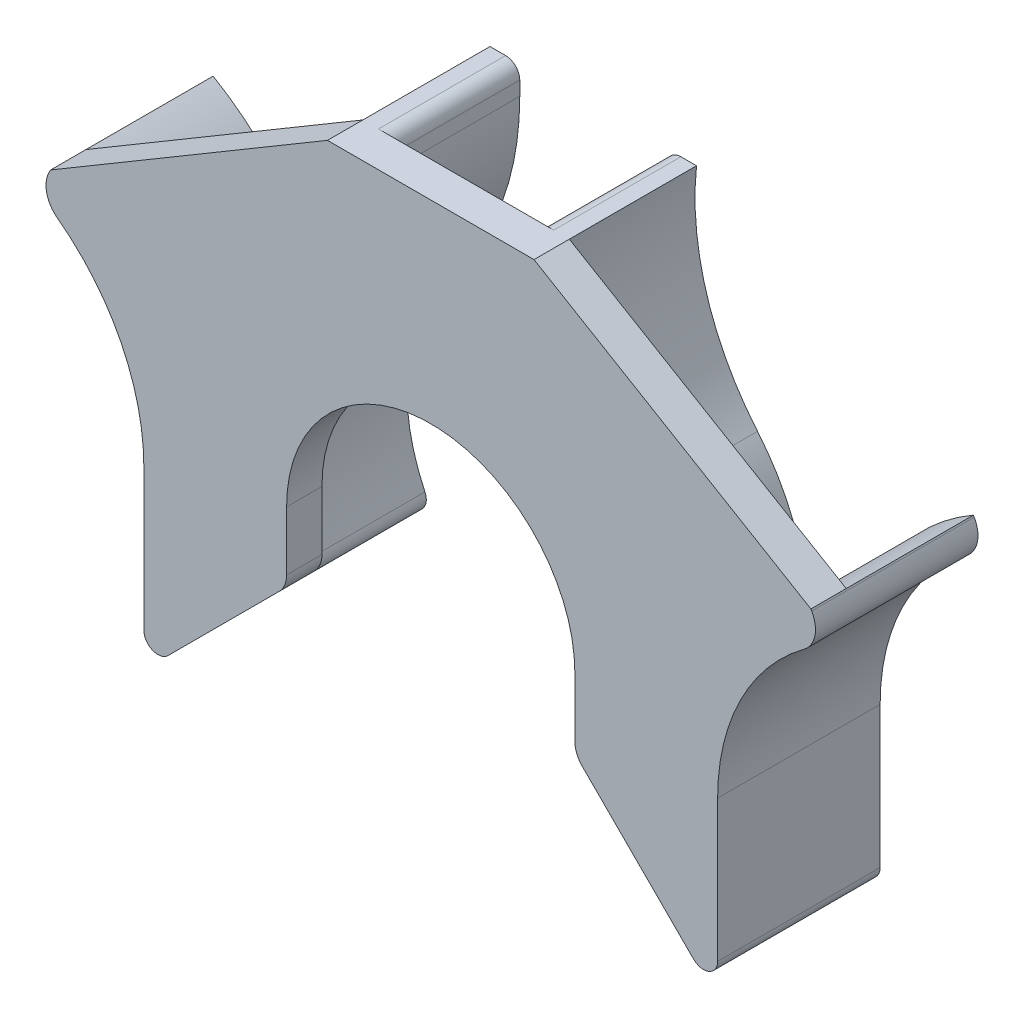
SolidWorks part; units mm, degrees
ref_plane "Front Plane" through (0, 0, 0) normal (0, 0, 1) x (1, 0, 0)
ref_plane "Top Plane" through (0, 0, 0) normal (0, 1, 0) x (1, 0, 0)
ref_plane "Right Plane" through (0, 0, 0) normal (1, 0, 0) x (0, 0, -1)
sketch "Sketch3" plane through (0, 0, 0) normal (0, 0, 1) x (1, 0, 0)
  point P0 (0, 0)
  line B0 (9.9412, 8.3769) -> (9.1765, 7.7326)
  line B1 (-9.1765, 7.7326) -> (-9.9412, 8.3769)
  line B2 (22, -13) -> (22, -2.5981)
  line B3 (20.5, -2.5981) -> (20.5, -13)
  line B4 (28.75, 9.0933) -> (28, 10.3923)
  line B5 (-28, 10.3923) -> (-28.75, 9.0933)
  line B6 (-20.5, -13) -> (-20.5, -2.5981)
  line B7 (-22, -2.5981) -> (-22, -13)
  line B8 (-10.5858, -5.5858) -> (-19.4142, -14.4142)
  line B9 (-19.4142, -14.4142) -> (-18.3536, -15.4749)
  line B10 (-18.3536, -15.4749) -> (-9.5251, -6.6464)
  line B11 (-10, 0) -> (-10, -4.1716)
  line B12 (-8.5, -4.1716) -> (-8.5, 0)
  line B13 (18.3536, -15.4749) -> (19.4142, -14.4142)
  line B14 (19.4142, -14.4142) -> (10.5858, -5.5858)
  line B15 (9.5251, -6.6464) -> (18.3536, -15.4749)
  line B16 (10, -4.1716) -> (10, 0)
  line B17 (8.5, 0) -> (8.5, -4.1716)
  line B18 (-4, 21.9089) -> (-4, 101.2523)
  line B19 (-4, 101.2523) -> (-5, 101.2523)
  line B20 (-5, 101.2523) -> (-5, 92)
  line B21 (-5, 92) -> (-5, 21.9089)
  line B22 (5, 101.2523) -> (4, 101.2523)
  line B23 (4, 101.2523) -> (4, 21.9089)
  line B24 (5, 21.9089) -> (5, 92)
  line B25 (5, 92) -> (5, 101.2523)
  line B26 (9.1765, 7.7326) -> (9.9412, 8.3769)
  line B27 (-9.9412, 8.3769) -> (-9.1765, 7.7326)
  arc B28 (-9.1765, 7.7326) -> (9.1765, 7.7326) centre (0, 0) ccw
  arc B29 (-9.9412, 8.3769) -> (9.9412, 8.3769) centre (0, 0) ccw
  arc B30 (18.9437, -14.9502) -> (20.5, -13) centre (18.5, -13) ccw
  arc B31 (28.75, 9.0933) -> (22, -2.5981) centre (35.5, -2.5981) ccw
  arc B32 (28, 10.3923) -> (20.5, -2.5981) centre (35.5, -2.5981) ccw
  arc B33 (-20.5, -2.5981) -> (-28, 10.3923) centre (-35.5, -2.5981) ccw
  arc B34 (-22, -2.5981) -> (-28.75, 9.0933) centre (-35.5, -2.5981) ccw
  arc B35 (-20.5, -13) -> (-18.9437, -14.9502) centre (-18.5, -13) ccw
  arc B36 (-10.5858, -5.5858) -> (-10, -4.1716) centre (-12, -4.1716) ccw
  arc B37 (-9.5251, -6.6464) -> (-8.5, -4.1716) centre (-12, -4.1716) ccw
  arc B38 (10, -4.1716) -> (10.5858, -5.5858) centre (12, -4.1716) ccw
  arc B39 (8.5, -4.1716) -> (9.5251, -6.6464) centre (12, -4.1716) ccw
  arc B40 (10, 0) -> (-10, 0) centre (0, 0) ccw
  arc B41 (8.5, 0) -> (-8.5, 0) centre (0, 0) ccw
  arc B42 (4, 21.9089) -> (9.1765, 7.7326) centre (26, 21.9089) ccw
  arc B43 (5, 21.9089) -> (9.9412, 8.3769) centre (26, 21.9089) ccw
  arc B44 (-9.1765, 7.7326) -> (-4, 21.9089) centre (-26, 21.9089) ccw
  arc B45 (-9.9412, 8.3769) -> (-5, 21.9089) centre (-26, 21.9089) ccw
  ellipse B46 centre (18.5, -13) end of major axis (15, -13) minor radius 2 (19.4068, -14.9317) -> (22, -13) ccw
  ellipse B47 centre (-18.5, -13) end of major axis (-15, -13) minor radius 2 (-22, -13) -> (-19.4068, -14.9317) ccw
  spline B48 degree 3 poles (18.9437, -14.9502) (19.099, -14.9148) (19.249, -14.9097) (19.4068, -14.9317) knots 0 0 0 0 1 1 1 1
  spline B49 degree 3 poles (-19.4068, -14.9317) (-19.249, -14.9097) (-19.099, -14.9148) (-18.9437, -14.9502) knots 0 0 0 0 1 1 1 1
sketch_block_instance "Block2-1"
sketch_block "Block2"
sketch "Sketch4" plane through (0, 0, 0) normal (0, 0, 1) x (1, 0, 0)
  line L10 (-20.3, -2.5981) -> (-20.3, -13)
  line L11 (-20.3, -2.5981) -> (-20.3, -13)
  line L14 (20.3, -2.5981) -> (20.3, -13)
  line L15 (20.3, -2.5981) -> (20.3, -13)
  line L22 (-10.7272, -5.4444) -> (-19.5556, -14.2728)
  line L23 (-11.5937, -6.3108) -> (-19.6596, -14.3767)
  line L25 (19.5556, -14.2728) -> (10.7272, -5.4444)
  line L26 (19.6596, -14.3767) -> (11.5937, -6.3108)
  line L29 (-5.2, 21.9089) -> (5.2, 21.9089)
  line L31 (-5.2, 92) -> (-5.2, 21.9089)
  line L32 (5.2, 21.9089) -> (5.2, 92)
  arc A11 (-20.3, -2.5981) -> (-27.9, 10.5655) centre (-35.5, -2.5981) ccw
  arc A12 (-20.3, -13) -> (-18.8993, -14.7552) centre (-18.5, -13) ccw
  arc A13 (-20.3, -2.5981) -> (-27.9, 10.5655) centre (-35.5, -2.5981) ccw
  arc A14 (-20.3, -13) -> (-19.6596, -14.3767) centre (-18.5, -13) ccw
  arc A19 (18.8993, -14.7552) -> (20.3, -13) centre (18.5, -13) ccw
  arc A20 (27.9, 10.5655) -> (20.3, -2.5981) centre (35.5, -2.5981) ccw
  arc A21 (19.6596, -14.3767) -> (20.3, -13) centre (18.5, -13) ccw
  arc A22 (27.9, 10.5655) -> (20.3, -2.5981) centre (35.5, -2.5981) ccw
  arc A34 (11.5937, -6.3108) -> (10.0941, 8.5058) centre (0, 0) ccw
  arc A37 (5.2, 21.9089) -> (10.0941, 8.5058) centre (26, 21.9089) ccw
  arc A38 (-10.0941, 8.5058) -> (-5.2, 21.9089) centre (-26, 21.9089) ccw
  arc A39 (-10.0941, 8.5058) -> (10.0941, 8.5058) centre (0, 0) ccw
  arc A40 (5.2, 21.9089) -> (10.0941, 8.5058) centre (26, 21.9089) ccw
  arc A41 (-10.0941, 8.5058) -> (-5.2, 21.9089) centre (-26, 21.9089) ccw
  arc A42 (-10.0941, 8.5058) -> (-11.5937, -6.3108) centre (0, 0) ccw
  dimension "D1" = 0.2
  dimension "D2" = 0.2
  dimension "D3" = 0.2
  dimension "D4" = 0.2
  dimension "D5" = 0.2
extrude "Extrude-Thin1" add sketch "Sketch4" against normal blind 9 thin
sketch "Sketch5" plane through (0, 0, 0) normal (0, 0, 1) x (1, 0, 0)
  line L12 (-26.9, 12.2976) -> (-27.9, 10.5655)
  line L13 (-20.3, -2.5981) -> (-20.3, -13)
  line L14 (-19.6596, -14.3767) -> (-11.5937, -6.3108)
  line L15 (-5.2, 21.9089) -> (5.2, 21.9089)
  line L16 (11.5937, -6.3108) -> (19.6596, -14.3767)
  line L17 (20.3, -13) -> (20.3, -2.5981)
  line L18 (27.9, 10.5655) -> (26.9, 12.2976)
  line L19 (18.3, -2.5981) -> (18.3, -10.1887)
  line L20 (18.3, -10.1887) -> (14.0091, -5.8978)
  line L21 (7.3067, 23.9089) -> (-7.3067, 23.9089)
  line L22 (-14.0091, -5.8978) -> (-18.3, -10.1887)
  line L23 (-18.3, -10.1887) -> (-18.3, -2.5981)
  line L24 (-26.9, 12.2976) -> (-27.9, 10.5655)
  line L25 (-20.3, -2.5981) -> (-20.3, -13)
  line L26 (-19.6596, -14.3767) -> (-11.5937, -6.3108)
  line L27 (-5.2, 21.9089) -> (5.2, 21.9089)
  line L28 (11.5937, -6.3108) -> (19.6596, -14.3767)
  line L29 (20.3, -13) -> (20.3, -2.5981)
  line L30 (27.9, 10.5655) -> (26.9, 12.2976)
  line L31 (18.3, -2.5981) -> (18.3, -10.1887)
  line L32 (18.3, -10.1887) -> (14.0091, -5.8978)
  line L33 (7.3067, 23.9089) -> (-7.3067, 23.9089)
  line L34 (-14.0091, -5.8978) -> (-18.3, -10.1887)
  line L35 (-18.3, -10.1887) -> (-18.3, -2.5981)
  line L39 (-26.9, 12.2976) -> (-7.3067, 23.9089)
  line L40 (7.3067, 23.9089) -> (26.9, 12.2976)
  line L43 (-10.7272, -5.4444) -> (-19.5556, -14.2728)
  line L44 (-10.2, 0) -> (-10.2, -4.1716)
  line L45 (10.2, -4.1716) -> (10.2, 0)
  line L46 (19.5556, -14.2728) -> (10.7272, -5.4444)
  line L47 (-10.7272, -5.4444) -> (-19.5556, -14.2728)
  line L48 (-10.2, 0) -> (-10.2, -4.1716)
  line L49 (10.2, -4.1716) -> (10.2, 0)
  line L50 (19.5556, -14.2728) -> (10.7272, -5.4444)
  arc A14 (-18.3, -2.5981) -> (-26.9, 12.2976) centre (-35.5, -2.5981) ccw
  arc A15 (-20.3, -2.5981) -> (-27.9, 10.5655) centre (-35.5, -2.5981) ccw
  arc A16 (-20.3, -13) -> (-19.6596, -14.3767) centre (-18.5, -13) ccw
  arc A17 (-10.0941, 8.5058) -> (-11.5937, -6.3108) centre (0, 0) ccw
  arc A18 (-10.0941, 8.5058) -> (-5.2, 21.9089) centre (-26, 21.9089) ccw
  arc A19 (5.2, 21.9089) -> (10.0941, 8.5058) centre (26, 21.9089) ccw
  arc A20 (11.5937, -6.3108) -> (10.0941, 8.5058) centre (0, 0) ccw
  arc A21 (19.6596, -14.3767) -> (20.3, -13) centre (18.5, -13) ccw
  arc A22 (27.9, 10.5655) -> (20.3, -2.5981) centre (35.5, -2.5981) ccw
  arc A23 (26.9, 12.2976) -> (18.3, -2.5981) centre (35.5, -2.5981) ccw
  arc A24 (14.0091, -5.8978) -> (11.6235, 9.7946) centre (0, 0) ccw
  arc A25 (7.3067, 23.9089) -> (11.6235, 9.7946) centre (26, 21.9089) ccw
  arc A26 (-11.6235, 9.7946) -> (-7.3067, 23.9089) centre (-26, 21.9089) ccw
  arc A27 (-11.6235, 9.7946) -> (-14.0091, -5.8978) centre (0, 0) ccw
  arc A28 (-18.3, -2.5981) -> (-26.9, 12.2976) centre (-35.5, -2.5981) ccw
  arc A29 (-20.3, -2.5981) -> (-27.9, 10.5655) centre (-35.5, -2.5981) ccw
  arc A30 (-20.3, -13) -> (-19.6596, -14.3767) centre (-18.5, -13) ccw
  arc A31 (-10.0941, 8.5058) -> (-11.5937, -6.3108) centre (0, 0) ccw
  arc A32 (-10.0941, 8.5058) -> (-5.2, 21.9089) centre (-26, 21.9089) ccw
  arc A33 (5.2, 21.9089) -> (10.0941, 8.5058) centre (26, 21.9089) ccw
  arc A34 (11.5937, -6.3108) -> (10.0941, 8.5058) centre (0, 0) ccw
  arc A35 (19.6596, -14.3767) -> (20.3, -13) centre (18.5, -13) ccw
  arc A36 (27.9, 10.5655) -> (20.3, -2.5981) centre (35.5, -2.5981) ccw
  arc A37 (26.9, 12.2976) -> (18.3, -2.5981) centre (35.5, -2.5981) ccw
  arc A38 (14.0091, -5.8978) -> (11.6235, 9.7946) centre (0, 0) ccw
  arc A39 (7.3067, 23.9089) -> (11.6235, 9.7946) centre (26, 21.9089) ccw
  arc A40 (-11.6235, 9.7946) -> (-7.3067, 23.9089) centre (-26, 21.9089) ccw
  arc A41 (-11.6235, 9.7946) -> (-14.0091, -5.8978) centre (0, 0) ccw
  arc A44 (-10.7272, -5.4444) -> (-10.2, -4.1716) centre (-12, -4.1716) ccw
  arc A45 (10.2, 0) -> (-10.2, 0) centre (0, 0) ccw
  arc A46 (10.2, -4.1716) -> (10.7272, -5.4444) centre (12, -4.1716) ccw
  arc A47 (-10.7272, -5.4444) -> (-10.2, -4.1716) centre (-12, -4.1716) ccw
  arc A48 (10.2, 0) -> (-10.2, 0) centre (0, 0) ccw
  arc A49 (10.2, -4.1716) -> (10.7272, -5.4444) centre (12, -4.1716) ccw
  arc M34 (-18.3, -2.5981) -> (-26.9, 12.2976) centre (-35.5, -2.5981) ccw
  line M35 (-26.9, 12.2976) -> (-27.9, 10.5655)
  arc M36 (-27.9, 10.5655) -> (-20.3, -2.5981) centre (-35.5, -2.5981) cw
  line M37 (-20.3, -2.5981) -> (-20.3, -13)
  arc M38 (-20.3, -13) -> (-19.6596, -14.3767) centre (-18.5, -13) ccw
  line M39 (-19.6596, -14.3767) -> (-11.5937, -6.3108)
  arc M40 (-11.5937, -6.3108) -> (-10.0941, 8.5058) centre (0, 0) cw
  arc M41 (-10.0941, 8.5058) -> (-5.2, 21.9089) centre (-26, 21.9089) ccw
  line M42 (-5.2, 21.9089) -> (5.2, 21.9089)
  arc M43 (5.2, 21.9089) -> (10.0941, 8.5058) centre (26, 21.9089) ccw
  arc M44 (10.0941, 8.5058) -> (11.5937, -6.3108) centre (0, 0) cw
  line M45 (11.5937, -6.3108) -> (19.6596, -14.3767)
  arc M46 (19.6596, -14.3767) -> (20.3, -13) centre (18.5, -13) ccw
  line M47 (20.3, -13) -> (20.3, -2.5981)
  arc M48 (20.3, -2.5981) -> (27.9, 10.5655) centre (35.5, -2.5981) cw
  line M49 (27.9, 10.5655) -> (26.9, 12.2976)
  arc M50 (26.9, 12.2976) -> (18.3, -2.5981) centre (35.5, -2.5981) ccw
  line M51 (18.3, -2.5981) -> (18.3, -10.1887)
  line M52 (18.3, -10.1887) -> (14.0091, -5.8978)
  arc M53 (14.0091, -5.8978) -> (11.6235, 9.7946) centre (0, 0) ccw
  arc M54 (11.6235, 9.7946) -> (7.3067, 23.9089) centre (26, 21.9089) cw
  line M55 (7.3067, 23.9089) -> (-7.3067, 23.9089)
  arc M56 (-7.3067, 23.9089) -> (-11.6235, 9.7946) centre (-26, 21.9089) cw
  arc M57 (-11.6235, 9.7946) -> (-14.0091, -5.8978) centre (0, 0) ccw
  line M58 (-14.0091, -5.8978) -> (-18.3, -10.1887)
  line M59 (-18.3, -10.1887) -> (-18.3, -2.5981)
  dimension "D1" = 0
  dimension "D2" = 0.2
extrude "Boss-Extrude1" add sketch "Sketch5" along normal blind 2.5 contours L39 M34 M59 M58 M57 M56 | L26 L28 M59 M34 M35 M36 M37 M38 M39 M40 M41 M42 M43 M44 M45 M46 M47 M48 M49 M50 M51 M52 M53 M54 M55 M56 M57 M58 | L40 M54 M53 M52 M51 M50 | L49 A49 L50 L47 A47 L48 A48 M44 M43 M42 M41 M40
sketch "Sketch7" plane through (0, 0, -9) normal (0, 0, 1) x (1, 0, 0)
  line L0 (-5, 92) -> (-5, 21.9089) construction
  line L6 (-5.2, 23.9089) -> (-5.2, 21.9089)
  line L8 (-5.2, 23.9089) -> (5.2, 23.9089)
  line L9 (5.2, 21.9089) -> (5.2, 92)
  line L10 (5.2, 21.9089) -> (5.2, 23.9089)
  line L11 (7.3067, 23.9089) -> (-7.3067, 23.9089) construction
  line L12 (-5.2, 21.9089) -> (5.2, 21.9089)
  arc A2 (-10.0941, 8.5058) -> (-5.2, 21.9089) centre (-26, 21.9089) ccw
  arc A3 (-10.0941, 8.5058) -> (-5.2, 21.9089) centre (-26, 21.9089) ccw
  arc A5 (5.2, 21.9089) -> (10.0941, 8.5058) centre (26, 21.9089) ccw
  arc A6 (5.2, 21.9089) -> (10.0941, 8.5058) centre (26, 21.9089) ccw
  line M35 (-7.3067, 23.9089) -> (7.3067, 23.9089)
  line M48 (5.2, 21.9089) -> (-5.2, 21.9089)
  dimension "D1" = 0.2
  dimension "D2" = 0.2
  dimension "D3" = 0.2
extrude "Cut-Extrude2" cut sketch "Sketch7" along normal offset from surface (9 mm away) 2.5 contours L10 L6 M48 M35 up to face at (0, 1.464, 2.5)
fillet "Fillet1" radius 2 2 edges at (27.9, 10.5655, -3.25) (-27.9, 10.5655, -3.25)
fillet "Fillet2" radius 1 4 edges at (20.3, -13, -3.25) (19.6596, -14.3767, -3.25) (-19.6596, -14.3767, -3.25) (-20.3, -13, -3.25)
fillet "Fillet3" radius 1 8 edges at (18.3, -10.1887, -4.5) (14.0091, -5.8978, -4.5) (-14.0091, -5.8978, -4.5) (-18.3, -10.1887, -4.5) (-11.5937, -6.3108, -4.5) (11.5937, -6.3108, -4.5) (-5.2, 23.9089, -4.5) (5.2, 23.9089, -4.5)
